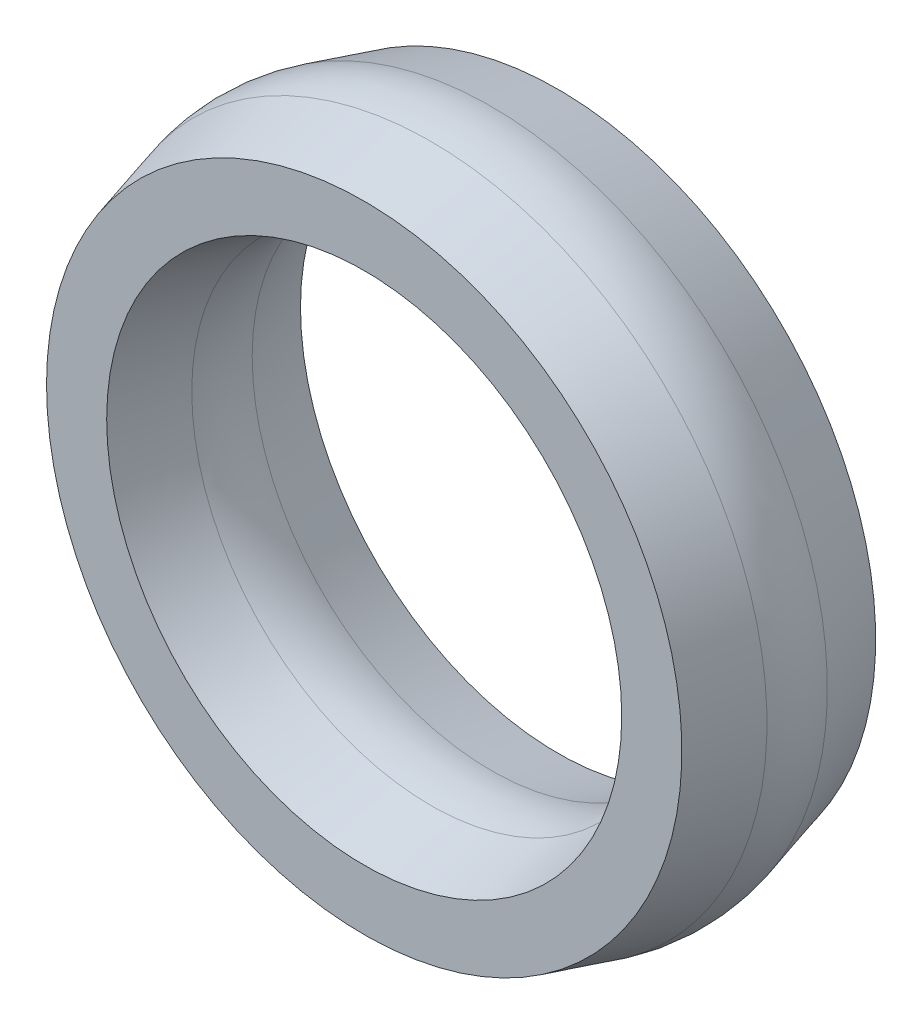
SolidWorks part; units mm, degrees
ref_plane "Front" through (0, 0, 0) normal (0, 0, 1) x (1, 0, 0)
ref_plane "Top" through (0, 0, 0) normal (0, 1, 0) x (1, 0, 0)
ref_plane "Right" through (0, 0, 0) normal (1, 0, 0) x (0, 0, -1)
sketch "Sketch1" plane through (0, 0, 0) normal (0, 1, 0) x (-1, 0, 0)
  line L0 (0, -7.25) -> (0, 7.5642) construction
  line L1 (0, -7.25) -> (-28.4986, -7.25) construction
  line L2 (-23.7675, 0) -> (-19.2675, 0)
  line L3 (-19.2675, 0) -> (-17.8911, -4.9896)
  line L4 (-21.5175, 0) -> (-21.5175, -7.25) construction
  line L5 (-19.2675, -14.5) -> (-17.8911, -9.5104)
  line L6 (-23.7675, -14.5) -> (-19.2675, -14.5)
  line L7 (-23.7675, -14.5) -> (-25.1439, -9.5104)
  line L8 (-23.7675, 0) -> (-25.1439, -4.9896)
  arc A0 (-17.8911, -9.5104) -> (-17.8911, -4.9896) centre (-26.085, -7.25) ccw
  arc A1 (-25.1439, -9.5104) -> (-25.1439, -4.9896) centre (-16.95, -7.25) cw
  point P12 (-17.2675, -7.25)
  point P17 (-21.5175, -14.5)
  dimension "s" = 8.5
  dimension "s1" = 4.5
revolve "Body" add sketch "Sketch1" angle 360 about L0
sketch "Sketch4" plane through (0, 0, 0) normal (0, 1, 0) x (-1, 0, 0)
  line L0 (-19.2675, 0) -> (-19.2675, -14.5)
  line L1 (-19.2675, 0) -> (-25.45, 0)
  line L2 (-25.45, 0) -> (-25.45, -14.5)
  line L3 (-25.45, -14.5) -> (-19.2675, -14.5)
  line L4 (0, 0) -> (0, 12.1247) construction
  arc A0 (-25.1439, -4.9896) -> (-25.1439, -9.5104) centre (-16.95, -7.25) ccw construction
revolve "Cut-Revolve1" [suppressed] cut sketch "Sketch4" angle 360 about L4
sketch "Sketch3" plane through (0, 0, 0) normal (0, 1, 0) x (1, 0, 0)
  line L0 (-16.95, 14.5) -> (-16.95, 0)
  line L1 (-16.95, 0) -> (-21.45, 0)
  line L2 (-21.45, 0) -> (-23.2, 4.35)
  line L3 (-23.2, 4.35) -> (-25.45, 5.8)
  line L4 (-25.45, 5.8) -> (-25.45, 8.7)
  line L5 (-25.45, 7.25) -> (-16.95, 7.25) construction
  line L6 (-23.2, 10.15) -> (-25.45, 8.7)
  line L7 (-21.45, 14.5) -> (-23.2, 10.15)
  line L8 (-16.95, 14.5) -> (-21.45, 14.5)
  line L10 (0, -15.5494) -> (0, 19.4432) construction
  dimension "D1" = 14.5
  dimension "s" = 8.5
  dimension "D3" = 2.9
  dimension "s1" = 4.5
  dimension "D5" = 2.25
  dimension "D6" = 5.8
  dimension "D7" = 50.9
revolve "Revolve1" [suppressed] add sketch "Sketch3" angle 360 about L10
fillet "Fillet1" [suppressed] radius 2.9
fillet "Fillet2" [suppressed] radius 2.9
equation "\"D4@Sketch1\" = \"s@Sketch1\""
equation "\"D3@Sketch3\" = \"D1@Sketch3\" / 5"
equation "\"D5@Sketch3\" = \"s1@Sketch3\" / 2"
equation "\"D6@Sketch3\" = \"D3@Sketch3\" * 2"
equation "\"D1@Fillet2\" = \"D3@Sketch3\""
equation "\"D1@Fillet1\" = \"D3@Sketch3\""
equation "\"D7@Sketch3\" = \"D@Sketch1\""
equation "\"D1@Sketch3\" = \"h@Sketch1\""
